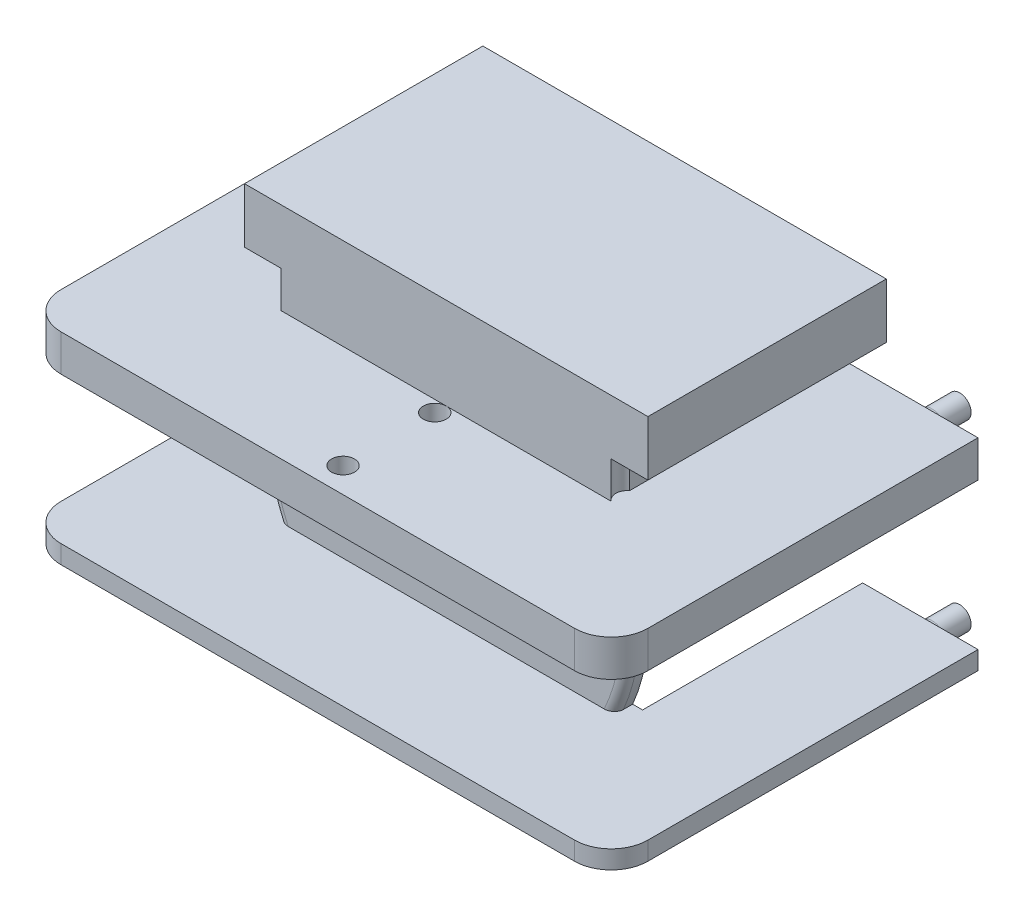
SolidWorks part; units mm, degrees
material "UNOBTANIUM"
ref_plane "Top Plane" through (0, 0, 0) normal (0, 0, 1) x (1, 0, 0)
ref_plane "Right Plane" through (0, 0, 0) normal (0, 1, 0) x (1, 0, 0)
ref_plane "Front Plane" through (0, 0, 0) normal (1, 0, 0) x (0, 0, -1)
ref_axis "x-axis" through (-17.6, 0, 0) along (1, 0, 0)
ref_axis "y-axis" through (0, -9.7375, 0) along (0, 1, 0)
ref_axis "z-axis" through (0, 0, 8.775) along (0, 0, -1)
sketch "Sketch1" plane through (0, 0, 0) normal (0, 0, 1) x (1, 0, 0)
  line L0 (-11, 6) -> (-11, 11)
  line L1 (-11, -6) -> (11, -6)
  line L2 (-11, -6) -> (-11, 6)
  line L3 (-11, 6) -> (11, 6) construction
  line L4 (11, -6) -> (11, 6)
  line L5 (-11, -6) -> (11, 6) construction
  line L6 (-11, 6) -> (11, -6) construction
  line L7 (-11, 11) -> (11, 11)
  line L8 (11, 11) -> (11, 6)
  circle A0 centre (0, 0) radius 9.25 construction
  point P0 (0, 0)
  dimension "D1" = 18.5
  dimension "D2" = 22
  dimension "D3" = 12
  dimension "D4" = 5
extrude "Boss-Extrude1" add sketch "Sketch1" along normal blind 1
sketch "Sketch2" plane through (0, 0, 0) normal (0, 0, -1) x (-1, 0, 0)
  circle A0 centre (0, 0) radius 1.475
  dimension "D1" = 2.95
extrude "Boss-Extrude2" add sketch "Sketch2" along normal blind 14
sketch "Sketch3" plane through (0, 0, 0) normal (0, 0, -1) x (-1, 0, 0)
  line L0 (11, -6) -> (-11, 6) construction
  circle A0 centre (0, 0) radius 1.8
  dimension "D1" = 3.6
extrude "Boss-Extrude3" add sketch "Sketch3" along normal blind 0.75
sketch "Sketch4" plane through (0, 0, 0) normal (0, 0, -1) x (-1, 0, 0)
  line L0 (11, -6) -> (-11, -6) construction
  line L1 (11, 11) -> (9, 11)
  line L2 (11, 11) -> (11, -6)
  line L3 (11, -6) -> (9, -6)
  line L4 (9, 11) -> (9, -6)
  line L5 (0, -6) -> (0, 11) construction
  line L7 (-9, 11) -> (-9, -6)
  line L8 (-11, -6) -> (-9, -6)
  line L9 (-11, 11) -> (-11, -6)
  line L10 (-11, 11) -> (-9, 11)
  line L11 (11, 11) -> (-11, 11) construction
  dimension "D1" = 2
extrude "Boss-Extrude4" add sketch "Sketch4" along normal blind 12
sketch "Sketch5" plane through (0, 0, 0) normal (0, 0, -1) x (-1, 0, 0)
  line L0 (-9, -6) -> (-9, 11) construction
  line L1 (9, 11) -> (-9, 11)
  line L2 (9, 11) -> (9, 9)
  line L3 (9, 9) -> (-9, 9)
  line L4 (-9, 11) -> (-9, 9)
  dimension "D1" = 2
extrude "Boss-Extrude5" add sketch "Sketch5" along normal up to surface (12 mm away) up to face at (-10, 2.5, -12)
sketch "Sketch6" plane through (11, 0, 0) normal (1, 0, 0) x (0, 0, -1)
  line L0 (-1, -6) -> (-1, 11) construction
  line L1 (12, -6) -> (-1, -6)
  line L2 (12, -6) -> (12, -4)
  line L3 (12, -4) -> (-1, -4)
  line L4 (-1, -6) -> (-1, -4)
  line L6 (12, 11) -> (12, -6) construction
  line L7 (-1, 6) -> (12, 6)
  line L8 (-1, 6) -> (-1, 4)
  line L9 (-1, 4) -> (12, 4)
  line L10 (12, 6) -> (12, 4)
  line L11 (5.5, 4) -> (5.5, -4) construction
  line L12 (0, 0) -> (5.5, 0) construction
  line L13 (0, -6) -> (0, 6) construction
  point P21 (5.5, 0)
  dimension "D1" = 2
extrude "Boss-Extrude6" add sketch "Sketch6" along normal blind 5
mirror "Mirror1" about plane through (0, 0, 0) normal (1, 0, 0) of "Boss-Extrude6"
sketch "Sketch7" plane through (0, 0, -12) normal (0, 0, -1) x (-1, 0, 0)
  line L0 (-9, -6) -> (-9, 9) construction
  line L1 (-9, 0) -> (-9, 9)
  line L2 (-9, 9) -> (0, 9)
  line L3 (-9, 0) -> (-9, -6)
  line L4 (-9, -6) -> (-6.7082, -6)
  line L5 (11, -6) -> (-11, -6) construction
  arc A0 (0, 9) -> (-6.7082, -6) centre (0, 0) ccw
  line M18 (-9, -6) -> (-9, 9)
  line M19 (-9, 9) -> (9, 9)
extrude "Boss-Extrude7" add sketch "Sketch7" against normal up to surface (12 mm away) contours A0 L4 M18 | A0 M19 M18 region at (8.3306, -4.5409, -12) region at (6.9897, 6.9897, -12) up to face at (1.8, 0, 0)
sketch "Sketch8" plane through (0, 0, -12) normal (0, 0, -1) x (-1, 0, 0)
  line L0 (-11, 4) -> (-9.1652, 4)
  line L1 (-11, 4) -> (-11, -4)
  line L2 (-11, -4) -> (-9.1652, -4)
  arc A1 (-9.1652, 4) -> (-9.1652, -4) centre (0, 0) ccw
  dimension "D1" = 10
extrude "Cut-Extrude1" cut sketch "Sketch8" against normal through all
sketch "Sketch9" plane through (0, 0, -12) normal (0, 0, -1) x (-1, 0, 0)
  line L0 (-16, -4) -> (-9.1652, -4) construction
  line L1 (-8.0623, 4) -> (-11, 4)
  line L2 (-8.0623, 4) -> (-8.0623, -4)
  line L3 (-8.0623, -4) -> (-11, -4)
  line L4 (-11, 4) -> (-11, -4)
  line L5 (-11, -6) -> (-11, 6) construction
  arc A0 (0, 9) -> (-6.7082, -6) centre (0, 0) ccw construction
  arc A1 (0, 9) -> (-6.7082, -6) centre (0, 0) ccw construction
extrude "Cut-Extrude2" cut sketch "Sketch9" against normal up to surface (12 mm away) up to face at (1.8, 0, 0)
mirror "Mirror2" about plane through (0, 0, 0) normal (1, 0, 0) of "Cut-Extrude2", "Cut-Extrude1", "Boss-Extrude7"
sketch "Sketch21" plane through (0, 0, -12) normal (0, 0, -1) x (-1, 0, 0)
  circle A0 centre (0, 0) radius 10.5
  circle A1 centre (0, 0) radius 9 construction
  circle A2 centre (0, 0) radius 1.8 construction
  circle A3 centre (0, 0) radius 1.8
  dimension "D1" = 1.5
extrude "Cut-Extrude11" cut sketch "Sketch21" against normal up to surface (12 mm away) up to face at (0, -0.7091, 0)
sketch "Sketch10" plane through (0, 0, 1) normal (0, 0, 1) x (1, 0, 0)
  line L0 (-16, -4) -> (-16, -6) construction
  line L1 (16, -6) -> (-16, -6)
  line L2 (16, -6) -> (16, -4)
  line L3 (16, -4) -> (-16, -4)
  line L4 (-16, -6) -> (-16, -4)
  line L5 (-16, -4) -> (-9.1652, -4) construction
  line L7 (-16, 6) -> (16, 6)
  line L8 (-16, 6) -> (-16, 4)
  line L9 (-16, 4) -> (16, 4)
  line L10 (16, 6) -> (16, 4)
extrude "Boss-Extrude8" add sketch "Sketch10" along normal blind 7
fillet "Fillet1" radius 0.5 2 edges at (10, 0, 1) (-10, 0, 1)
sketch "Sketch11" plane through (0, 0, -12) normal (0, 0, -1) x (-1, 0, 0)
  line L0 (-16, -5) -> (-13, -5) construction
  line L1 (-16, -6) -> (-16, -4) construction
  circle A0 centre (-13, -5) radius 0.625
  dimension "D1" = 1.25
  dimension "D2" = 3
extrude "Boss-Extrude9" add sketch "Sketch11" along normal blind 2
sketch "Sketch14" plane through (0, 0, -12) normal (0, 0, -1) x (-1, 0, 0)
  line L1 (11, 6) -> (9, 6)
  line L2 (11, 6) -> (11, 8)
  line L3 (11, 8) -> (9, 8)
  line L4 (9, 6) -> (9, 8)
  line L5 (-11, 6) -> (-9, 6)
  line L6 (-11, 6) -> (-11, 8)
  line L7 (-11, 8) -> (-9, 8)
  line L8 (-9, 6) -> (-9, 8)
  dimension "D1" = 18
  dimension "D2" = 2
extrude "Cut-Extrude5" cut sketch "Sketch14" against normal through all
sketch "Sketch12" plane through (0, 0, -12) normal (0, 0, -1) x (-1, 0, 0)
  line L0 (-16, -5) -> (-13, -5) construction
  line L1 (-16, -6) -> (-16, -4) construction
  line L3 (16, -5) -> (13, -5) construction
  line L4 (16, -6) -> (16, -4) construction
  circle A0 centre (13, -5) radius 0.725
  circle A1 centre (-13, -5) radius 0.625 construction
  circle A2 centre (-13, -5) radius 0.625 construction
  dimension "D1" = 1.45
  dimension "D2" = 1.25
extrude "Cut-Extrude3" cut sketch "Sketch12" against normal blind 2.5
sketch "Sketch16" plane through (0, 6, 0) normal (0, 1, 0) x (1, 0, 0)
  line L0 (-9, -1) -> (-9, 12) construction
  line L1 (-9, 0) -> (-9, -1)
  arc A1 (-9, 0) -> (-9, -1) centre (-9.375, -0.5) cw
  dimension "D1" = 0.25
  dimension "D2" = 1
extrude "Cut-Extrude6" cut sketch "Sketch16" along normal blind 2
mirror "Mirror3" about plane through (0, 0, 0) normal (0, 1, 0) of "Boss-Extrude9", "Cut-Extrude3"
mirror "Mirror4" about plane through (0, 0, 0) normal (1, 0, 0) of "Cut-Extrude6"
fillet "Fillet2" radius 0.5 2 edges at (12.375, 5, -12) (13.625, -5, -12)
fillet "Fillet3" radius 0.5 2 edges at (-13.725, 5, -12) (-13.725, -5, -12)
fillet "Fillet4" radius 2 4 edges at (16, -5, 8) (16, 5, 8) (-16, -5, 8) (-16, 5, 8)
sketch "Sketch17" plane through (0, -6, 0) normal (0, -1, 0) x (1, 0, 0)
  line L0 (-16, 6) -> (-16, -12) construction
  line L1 (-14, 8) -> (14, 8) construction
  line L2 (16, 6) -> (16, -12) construction
  line L3 (-16, 6) -> (-16, -12)
  line L4 (-14, 8) -> (14, 8)
  line L5 (16, 6) -> (16, -12)
  line L6 (14.5, 6) -> (14.5, -12)
  line L8 (-14, 6.5) -> (14, 6.5)
  line L9 (-14.5, 6) -> (-14.5, -12)
  line L10 (14.5, -12) -> (16, -12)
  line L11 (-14.5, -12) -> (-16, -12)
  arc A0 (-14, 8) -> (-16, 6) centre (-14, 6) ccw construction
  arc A1 (16, 6) -> (14, 8) centre (14, 6) ccw construction
  arc A2 (-14, 8) -> (-16, 6) centre (-14, 6) ccw
  arc A3 (16, 6) -> (14, 8) centre (14, 6) ccw
  arc A4 (14.5, 6) -> (14, 6.5) centre (14, 6) ccw
  arc A5 (-14, 6.5) -> (-14.5, 6) centre (-14, 6) ccw
  dimension "D1" = 1.5
extrude "Cut-Extrude7" cut sketch "Sketch17" against normal blind 1 and the other way through all
sketch "Sketch19" plane through (0, 6, 0) normal (0, 1, 0) x (1, 0, 0)
  line L0 (9, -1) -> (-9, -1) construction
  line L1 (0, -1.625) -> (0, -1) construction
  line L2 (9, -1) -> (-9, -1) construction
  circle A0 centre (0, -1.625) radius 0.625
  circle A1 centre (0, -6.625) radius 0.625
  point P4 (0, -1)
  dimension "D1" = 1.25
  dimension "D2" = 5
extrude "Cut-Extrude9" cut sketch "Sketch19" against normal up to surface (2 mm away) up to face at (-0.0266, 4, -3.1997)
sketch "Sketch20" plane through (0, 0, -12) normal (0, 0, -1) x (-1, 0, 0)
  line L0 (-9, 8) -> (-11, 8) construction
  line L1 (-11, 11) -> (-9, 11)
  line L2 (-11, 11) -> (-11, 8)
  line L3 (-11, 8) -> (-9, 8)
  line L4 (-9, 11) -> (-9, 8)
  line L5 (11, 11) -> (-11, 11) construction
  line L6 (11, 8) -> (9, 8)
  line L7 (11, 8) -> (11, 11)
  line L8 (11, 11) -> (9, 11)
  line L9 (9, 8) -> (9, 11)
  dimension "D1" = 2
fillet "Fillet5" radius 0.4 1 edges at (-1.475, 0, -14)
sketch "Sketch22" plane through (0, 0, -12) normal (0, 0, -1) x (-1, 0, 0)
  line L0 (13, -6) -> (13, -4) construction
  line L1 (12.2925, -6) -> (13.7075, -6) construction
  line L2 (13.7075, -4) -> (12.2925, -4) construction
  line L3 (12.6, -6) -> (12.6, -4)
  line L4 (13.4, -6) -> (13.4, -4)
  arc A0 (12.6, -6) -> (13.4, -6) centre (13, -6) ccw
  arc A1 (13.4, -4) -> (12.6, -4) centre (13, -4) ccw
  point P6 (13, -5)
  dimension "D1" = 0.8
extrude "Cut-Extrude12" cut sketch "Sketch22" against normal up to surface (2.5 mm away) up to face at (-13.725, -5, -9.5)
mirror "Mirror5" about plane through (0, 0, 0) normal (0, 1, 0) of "Cut-Extrude12"
equation "\"D1@Sketch12\"=\"D2@Sketch12\"+.2"
